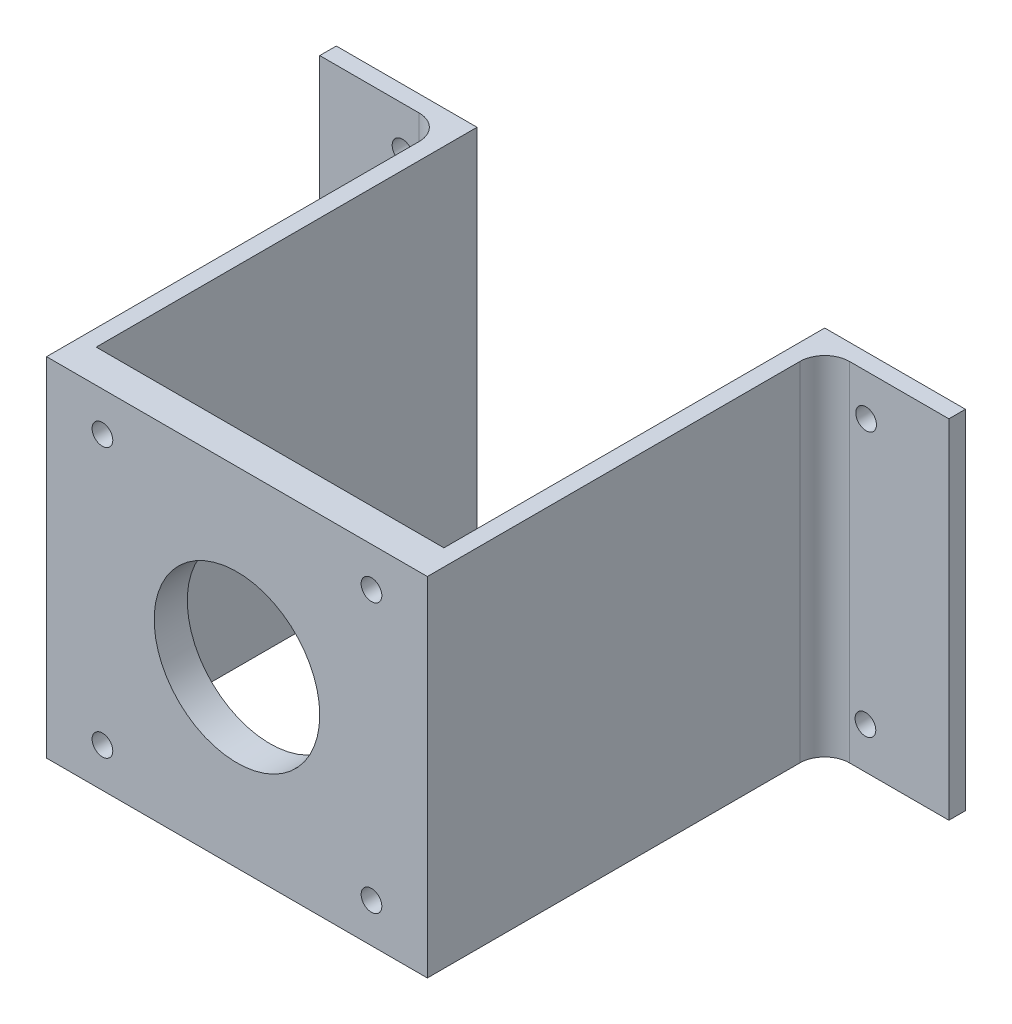
SolidWorks part; units mm, degrees
ref_plane "Alzado" through (0, 0, 0) normal (0, 0, 1) x (1, 0, 0)
ref_plane "Planta" through (0, 0, 0) normal (0, 1, 0) x (1, 0, 0)
ref_plane "Vista lateral" through (0, 0, 0) normal (1, 0, 0) x (0, 0, -1)
sketch "Croquis1" plane through (0, 0, 0) normal (0, 0, 1) x (1, 0, 0)
  line L1 (-84.7498, 36.6204) -> (-38.7498, 36.6204)
  line L2 (-84.7498, 36.6204) -> (-84.7498, -5.3796)
  line L3 (-84.7498, -5.3796) -> (-38.7498, -5.3796)
  line L4 (-38.7498, 36.6204) -> (-38.7498, -5.3796)
  line L5 (-84.7498, 36.6204) -> (-38.7498, -5.3796) construction
  line L6 (-84.7498, -5.3796) -> (-38.7498, 36.6204) construction
  point P0 (-61.7498, 15.6204)
  dimension "D1" = 46
extrude "Saliente-Extruir1" add sketch "Croquis1" along normal blind 4
sketch "Croquis3" plane through (0, 0, 0) normal (0, 0, -1) x (-1, 0, 0)
  line L0 (82.7498, 36.6204) -> (84.7498, 36.6204)
  line L1 (38.7498, 36.6204) -> (84.7498, 36.6204) construction
  line L2 (82.7498, 36.6204) -> (82.7498, -5.3796)
  line L3 (84.7498, -5.3796) -> (38.7498, -5.3796) construction
  line L4 (82.7498, -5.3796) -> (84.7498, -5.3796)
  line L5 (84.7498, 36.6204) -> (84.7498, -5.3796)
  line L6 (38.7498, 36.6204) -> (40.7498, 36.6204)
  line L7 (38.7498, 36.6204) -> (38.7498, -5.3796)
  line L8 (38.7498, -5.3796) -> (38.7498, 36.6204) construction
  line L9 (40.7498, 36.6204) -> (40.7498, -5.3796)
  line L10 (38.7498, -5.3796) -> (40.7498, -5.3796)
extrude "Saliente-Extruir2" add sketch "Croquis3" along normal blind 46
sketch "Croquis4" plane through (-84.7498, 0, 0) normal (-1, 0, 0) x (0, 0, 1)
  line L0 (-46, 36.6204) -> (-44, 36.6204)
  line L1 (4, 36.6204) -> (-46, 36.6204) construction
  line L2 (-44, 36.6204) -> (-44, -5.3796)
  line L3 (4, -5.3796) -> (-46, -5.3796) construction
  line L4 (-44, -5.3796) -> (-46, -5.3796)
  line L5 (-46, -5.3796) -> (-46, 36.6204)
extrude "Saliente-Extruir3" add sketch "Croquis4" along normal blind 15 contours L5 L0 L2 L4
sketch "Croquis6" plane through (-38.7498, 0, 0) normal (1, 0, 0) x (0, 0, -1)
  line L0 (46, 36.6204) -> (44, 36.6204)
  line L1 (-4, 36.6204) -> (46, 36.6204) construction
  line L2 (44, 36.6204) -> (44, -5.3796)
  line L3 (-4, -5.3796) -> (46, -5.3796) construction
  line L4 (44, -5.3796) -> (46, -5.3796)
  line L5 (46, -5.3796) -> (46, 36.6204)
extrude "Saliente-Extruir4" add sketch "Croquis6" along normal blind 15
sketch "Croquis7" plane through (0, 0, 4) normal (0, 0, 1) x (1, 0, 0)
  line L0 (-38.7498, -5.3796) -> (-45.4998, -5.3796)
  line L1 (-84.7498, -5.3796) -> (-38.7498, -5.3796) construction
  line L2 (-45.4998, -5.3796) -> (-45.4998, -0.6296)
  line L3 (-45.4998, -0.6296) -> (-38.7498, -0.6296)
  line L4 (-38.7498, -5.3796) -> (-38.7498, 36.6204) construction
  line L5 (-38.7498, -0.6296) -> (-38.7498, -5.3796)
  circle A0 centre (-45.4998, -0.6296) radius 1.25
  dimension "D1" = 2.5
  dimension "D2" = 6.75
sketch "Croquis8" plane through (0, 0, 4) normal (0, 0, 1) x (1, 0, 0)
  line L0 (-84.7498, -5.3796) -> (-77.9998, -5.3796)
  line L1 (-84.7498, -5.3796) -> (-38.7498, -5.3796) construction
  line L2 (-77.9998, -5.3796) -> (-77.9998, -0.6296)
  line L3 (-77.9998, -0.6296) -> (-84.7498, -0.6296)
  line L4 (-84.7498, 36.6204) -> (-84.7498, -5.3796) construction
  line L5 (-84.7498, -0.6296) -> (-84.7498, -5.3796)
  line L6 (-84.7498, 36.6204) -> (-84.7498, 31.8704)
  line L7 (-84.7498, 36.6204) -> (-84.7498, -5.3796) construction
  line L8 (-84.7498, 31.8704) -> (-77.9998, 31.8704)
  line L9 (-77.9998, 31.8704) -> (-77.9998, 36.6204)
  line L10 (-38.7498, 36.6204) -> (-84.7498, 36.6204) construction
  line L11 (-77.9998, 36.6204) -> (-84.7498, 36.6204)
  line L12 (-38.7498, 36.6204) -> (-38.7498, 31.8704)
  line L13 (-38.7498, -5.3796) -> (-38.7498, 36.6204) construction
  line L14 (-38.7498, 36.6204) -> (-45.4998, 36.6204)
  line L15 (-45.4998, 36.6204) -> (-45.4998, 31.8704) construction
  line L16 (-45.4998, 31.8704) -> (-38.7498, 31.8704) construction
  circle A0 centre (-45.4998, 31.8704) radius 1.25
  circle A1 centre (-77.9998, 31.8704) radius 1.25
  circle A2 centre (-77.9998, -0.6296) radius 1.25
  dimension "D1" = 2.5
  dimension "D2" = 2.5
  dimension "D3" = 2.5
sketch "Croquis9" plane through (0, 0, 4) normal (0, 0, 1) x (1, 0, 0)
extrude "Cortar-Extruir1" cut sketch "Croquis8" against normal blind 15 contours A0 | L2 A2 L3 | L3 A2 L2 | A1 region at (-78.5303, -1.1601, 4) region at (-77.823, -0.4528, 4) region at (-45.4998, 31.8704, 4)
extrude "Cortar-Extruir2" cut sketch "Croquis7" against normal blind 15 contours L3 A0 L2 | L2 A0 L3 region at (-45.6766, -0.4528, 4) region at (-44.9693, -1.1601, 4)
sketch "Croquis10" plane through (0, 0, -44) normal (0, 0, 1) x (1, 0, 0)
  line L0 (-23.7498, 36.6204) -> (-38.7498, 36.6204) construction
  line L1 (-33.8299, -0.3796) -> (-33.7498, -5.3796) construction
  line L2 (-23.7498, -5.3796) -> (-38.7498, -5.3796) construction
  line L3 (-33.7498, -5.3796) -> (-38.7498, -5.3796) construction
  line L10 (-38.7498, -5.3796) -> (-38.7498, -0.3796) construction
  line L11 (-38.7498, 36.6204) -> (-38.7498, -5.3796) construction
  line L12 (-38.7498, -0.3796) -> (-33.8299, -0.3796) construction
  circle A0 centre (-33.7498, 31.6204) radius 1.25
  circle A3 centre (-33.8299, -0.3796) radius 1.25
  dimension "D5" = 2.5
  dimension "D4" = 2.5
  dimension "D1" = 15
  dimension "D2" = 5
  dimension "D3" = 5
extrude "Cortar-Extruir4" cut sketch "Croquis10" against normal blind 15
ref_plane "Plano4" through (-61.7498, 0, 0) normal (1, 0, 0) x (0, 0, -1)
mirror "Simetría1" about plane through (-61.7498, 0, 0) normal (1, 0, 0) of "Cortar-Extruir4"
fillet "Redondeo1" radius 3 1 edges at (-84.7498, 15.6204, -44)
fillet "Redondeo2" radius 3 1 edges at (-38.7498, 15.6204, -44)
sketch "Croquis11" plane through (0, 0, 4) normal (0, 0, 1) x (1, 0, 0)
  line L0 (-84.7498, 15.6204) -> (-38.7498, 15.6204) construction
  line L1 (-84.7498, 36.6204) -> (-84.7498, -5.3796) construction
  line L2 (-38.7498, -5.3796) -> (-38.7498, 36.6204) construction
  line L3 (-61.7498, 36.6204) -> (-61.7498, -5.2663) construction
  line L4 (-38.7498, 36.6204) -> (-84.7498, 36.6204) construction
  line L5 (-61.7498, -23.1) -> (-61.7498, 23.1) construction
  circle A0 centre (-61.7498, 15.6204) radius 10
  dimension "D1" = 20
extrude "Cortar-Extruir5" cut sketch "Croquis11" against normal blind 15
